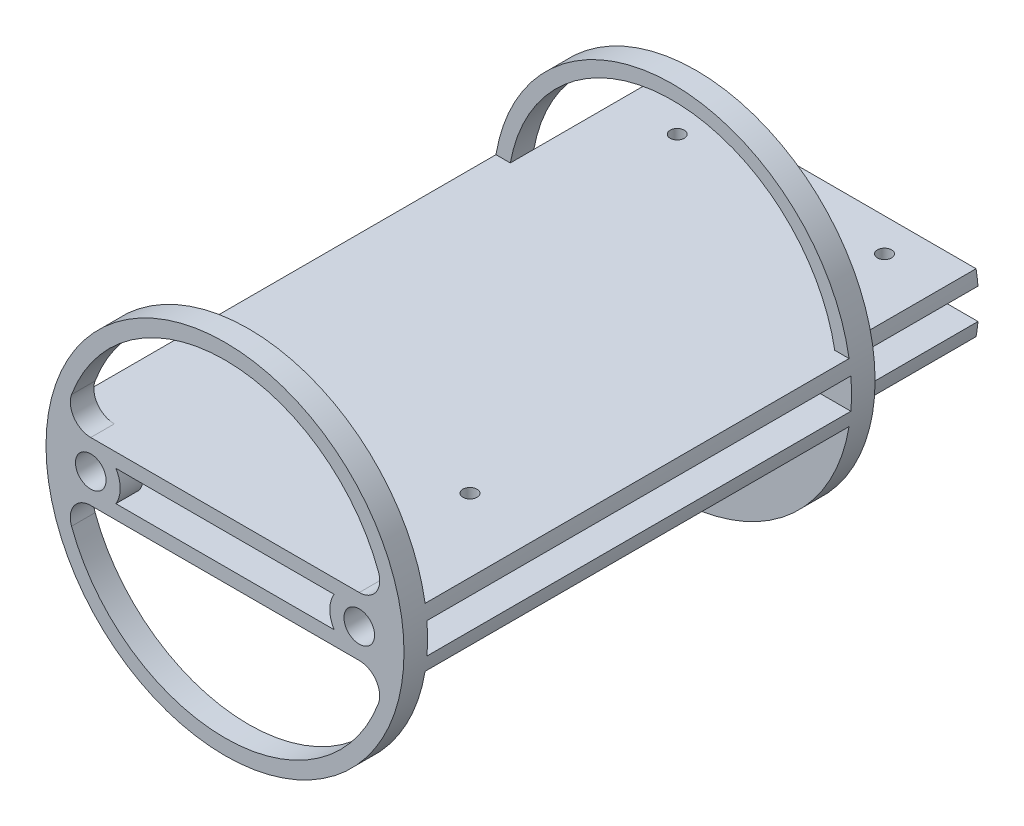
SolidWorks part; units mm, degrees
material "ABS"
ref_plane "Front Plane" through (0, 0, 0) normal (0, 0, 1) x (1, 0, 0)
ref_plane "Top Plane" through (0, 0, 0) normal (0, 1, 0) x (1, 0, 0)
ref_plane "Right Plane" through (0, 0, 0) normal (1, 0, 0) x (0, 0, -1)
sketch "Sketch1" plane through (0, 0, 0) normal (0, 0, 1) x (1, 0, 0)
  line L0 (-28.5, 0) -> (28.5, 0) construction
  line L1 (-34.5977, -3.25) -> (-33.8385, -3.25) construction
  line L2 (-28.5, -6.25) -> (28.5, -6.25)
  line L3 (-34.5977, -3.25) -> (-37.8608, -3.25) construction
  line L4 (34.5977, -3.25) -> (37.8608, -3.25) construction
  line L5 (-28.5, 6.25) -> (28.5, 6.25)
  line L6 (23.1615, 3.25) -> (-23.1615, 3.25)
  line L7 (-33.8385, -3.25) -> (-28.5, -3.25) construction
  line L8 (-23.1615, -3.25) -> (23.1615, -3.25)
  line L9 (-28.5, -3.25) -> (-23.1615, -3.25) construction
  line L10 (-34.1833, -6.25) -> (-28.5, -6.25) construction
  line L11 (23.1615, -3.25) -> (28.5, -3.25) construction
  line L12 (33.8385, -3.25) -> (34.5977, -3.25)
  line L13 (28.5, -3.25) -> (33.8385, -3.25) construction
  line L14 (28.5, -6.25) -> (34.1833, -6.25) construction
  circle A0 centre (0, 0) radius 38
  arc A1 (32.5722, 12.1083) -> (-32.5722, 12.1083) centre (0, 0) ccw
  circle A2 centre (-28.5, 0) radius 3.25
  circle A3 centre (28.5, 0) radius 3.25
  arc A4 (-23.1615, -3.25) -> (-23.1615, 3.25) centre (-28.5, 0) ccw
  arc A6 (-32.5722, 12.1083) -> (-28.5, 6.25) centre (-28.5, 10.5945) ccw
  arc A7 (-28.5, -6.25) -> (-32.5722, -12.1083) centre (-28.5, -10.5945) ccw
  arc A8 (28.5, 6.25) -> (32.5722, 12.1083) centre (28.5, 10.5945) ccw
  arc A9 (32.5722, -12.1083) -> (28.5, -6.25) centre (28.5, -10.5945) ccw
  arc A10 (34.75, 0) -> (32.5722, 12.1083) centre (0, 0) ccw construction
  arc A11 (-33.8385, -3.25) -> (-28.5, -6.25) centre (-28.5, 0) ccw construction
  arc A12 (28.5, -6.25) -> (33.8385, -3.25) centre (28.5, 0) ccw construction
  arc A13 (34.5977, -3.25) -> (34.75, 0) centre (0, 0) ccw construction
  arc A14 (-32.5722, 12.1083) -> (-34.75, 0) centre (0, 0) ccw construction
  arc A15 (-32.5722, -12.1083) -> (32.5722, -12.1083) centre (0, 0) ccw
  arc A16 (-34.5977, -3.25) -> (-34.1833, -6.25) centre (0, 0) ccw construction
  arc A17 (-34.75, 0) -> (-33.8385, -3.25) centre (-28.5, 0) ccw construction
  arc A18 (-34.75, 0) -> (-34.5977, -3.25) centre (0, 0) ccw construction
  arc A19 (-34.5977, -3.25) -> (-34.1833, -6.25) centre (0, 0) ccw construction
  arc A20 (-32.5722, -12.1083) -> (32.5722, -12.1083) centre (0, 0) ccw
  arc A21 (34.1833, -6.25) -> (34.5977, -3.25) centre (0, 0) ccw construction
  arc A22 (32.5722, 12.1083) -> (-32.5722, 12.1083) centre (0, 0) ccw
  arc A24 (23.1615, 3.25) -> (23.1615, -3.25) centre (28.5, 0) ccw
  arc A25 (-34.1833, -6.25) -> (-32.5722, -12.1083) centre (0, 0) ccw construction
  arc A26 (-34.5977, -3.25) -> (-34.1833, -6.25) centre (0, 0) ccw construction
  arc A27 (-32.5722, -12.1083) -> (32.5722, -12.1083) centre (0, 0) ccw
  arc A28 (-34.75, 0) -> (-34.5977, -3.25) centre (0, 0) ccw construction
  arc A29 (-34.75, 0) -> (-34.5977, -3.25) centre (0, 0) ccw construction
  arc A30 (-34.1833, -6.25) -> (-32.5722, -12.1083) centre (0, 0) ccw construction
  arc A31 (-34.1833, -6.25) -> (-32.5722, -12.1083) centre (0, 0) ccw construction
  arc A32 (-32.5722, 12.1083) -> (-34.75, 0) centre (0, 0) ccw construction
  arc A33 (-32.5722, 12.1083) -> (-34.75, 0) centre (0, 0) ccw construction
  arc A34 (-28.5, -6.25) -> (-23.1615, -3.25) centre (-28.5, 0) ccw construction
  arc A35 (23.1615, -3.25) -> (28.5, -6.25) centre (28.5, 0) ccw construction
  arc A36 (32.5722, -12.1083) -> (34.1833, -6.25) centre (0, 0) ccw construction
  arc A37 (32.5722, -12.1083) -> (34.1833, -6.25) centre (0, 0) ccw construction
  arc A38 (32.5722, 12.1083) -> (-32.5722, 12.1083) centre (0, 0) ccw
  arc A39 (32.5722, -12.1083) -> (34.1833, -6.25) centre (0, 0) ccw construction
  arc A40 (34.1833, -6.25) -> (34.5977, -3.25) centre (0, 0) ccw construction
  arc A41 (34.1833, -6.25) -> (34.5977, -3.25) centre (0, 0) ccw construction
  arc A42 (34.5977, -3.25) -> (34.75, 0) centre (0, 0) ccw construction
  arc A43 (34.5977, -3.25) -> (34.75, 0) centre (0, 0) ccw construction
  arc A44 (33.8385, -3.25) -> (34.75, 0) centre (28.5, 0) ccw construction
  arc A45 (34.75, 0) -> (32.5722, 12.1083) centre (0, 0) ccw construction
  arc A46 (34.75, 0) -> (32.5722, 12.1083) centre (0, 0) ccw construction
  point P8 (0, 0)
  dimension "D2" = 6.5
  dimension "D3" = 3
  dimension "D4" = 76
  dimension "D1" = 57
extrude "Boss-Extrude1" add sketch "Sketch1" along normal blind 5 contours A0 A15 A7 L2 A9 A8 L5 A6 A1 A3 A2 L6 A24 L8 A4 region at (-36.9252, 0, 0)
sketch "Sketch2" plane through (0, 0, 0) normal (0, 0, -1) x (-1, 0, 0)
  line L0 (-37.8608, -3.25) -> (37.8608, -3.25)
  line L1 (37.4825, -6.25) -> (-37.4825, -6.25)
  line L4 (-37.4825, 6.25) -> (37.4825, 6.25)
  line L5 (-37.8608, 3.25) -> (37.8608, 3.25)
  line L8 (23.1615, -3.25) -> (-23.1615, -3.25) construction
  line L9 (28.5, -6.25) -> (-28.5, -6.25) construction
  line L10 (28.5, 6.25) -> (-28.5, 6.25) construction
  line L11 (-23.1615, 3.25) -> (23.1615, 3.25) construction
  arc A1 (-37.8608, -3.25) -> (-37.4825, -6.25) centre (0, 0) ccw
  arc A2 (37.8608, 3.25) -> (37.4825, 6.25) centre (0, 0) ccw
  arc A3 (-37.4825, -6.25) -> (37.4825, -6.25) centre (0, 0) ccw construction
  arc A4 (37.4825, -6.25) -> (37.8608, -3.25) centre (0, 0) ccw
  arc A5 (37.4825, 6.25) -> (-37.4825, 6.25) centre (0, 0) ccw construction
  arc A6 (-37.4825, 6.25) -> (-37.8608, 3.25) centre (0, 0) ccw
  arc A7 (-37.8608, 3.25) -> (-37.8608, -3.25) centre (0, 0) ccw construction
  arc A8 (37.8608, -3.25) -> (37.8608, 3.25) centre (0, 0) ccw construction
  circle A9 centre (0, 0) radius 38 construction
extrude "Boss-Extrude2" add sketch "Sketch2" along normal blind 90
sketch "Sketch3" plane through (0, 0, -90) normal (0, 0, -1) x (-1, 0, 0)
  arc A1 (-28.5, 3.25) -> (-28.5, -3.25) centre (-28.5, 0) ccw construction
  arc A9 (-28.5, -3.25) -> (-28.5, 3.25) centre (-28.5, 0) ccw construction
  arc A10 (28.5, 3.25) -> (28.5, -3.25) centre (28.5, 0) ccw construction
  arc A15 (28.5, -3.25) -> (28.5, 3.25) centre (28.5, 0) ccw construction
  arc A33 (37.8608, 3.25) -> (37.4825, 6.25) centre (0, 0) ccw construction
  arc A58 (37.8608, -3.25) -> (37.8608, 3.25) centre (0, 0) ccw construction
  arc A59 (37.4825, -6.25) -> (37.8608, -3.25) centre (0, 0) ccw construction
  arc A60 (-37.4825, -6.25) -> (37.4825, -6.25) centre (0, 0) ccw construction
  arc A61 (-37.8608, -3.25) -> (-37.4825, -6.25) centre (0, 0) ccw construction
  arc A62 (-37.8608, 3.25) -> (-37.8608, -3.25) centre (0, 0) ccw construction
  arc A63 (-37.4825, 6.25) -> (-37.8608, 3.25) centre (0, 0) ccw construction
  arc A64 (37.4825, 6.25) -> (-37.4825, 6.25) centre (0, 0) ccw construction
  arc A65 (-28.5, 3.25) -> (-28.5, -3.25) centre (-28.5, 0) ccw
  arc A66 (-28.5, -3.25) -> (-28.5, 3.25) centre (-28.5, 0) ccw
  arc A67 (28.5, 3.25) -> (28.5, -3.25) centre (28.5, 0) ccw
  arc A68 (28.5, -3.25) -> (28.5, 3.25) centre (28.5, 0) ccw
  arc A69 (37.8608, 3.25) -> (37.4825, 6.25) centre (0, 0) ccw
  arc A70 (37.8608, -3.25) -> (37.8608, 3.25) centre (0, 0) ccw
  arc A71 (37.4825, -6.25) -> (37.8608, -3.25) centre (0, 0) ccw
  arc A72 (-37.4825, -6.25) -> (37.4825, -6.25) centre (0, 0) ccw
  arc A73 (-37.8608, -3.25) -> (-37.4825, -6.25) centre (0, 0) ccw
  arc A74 (-37.8608, 3.25) -> (-37.8608, -3.25) centre (0, 0) ccw
  arc A75 (-37.4825, 6.25) -> (-37.8608, 3.25) centre (0, 0) ccw
  arc A76 (37.4825, 6.25) -> (-37.4825, 6.25) centre (0, 0) ccw
extrude "Boss-Extrude3" add sketch "Sketch3" along normal blind 5
sketch "Sketch4" plane through (0, -6.25, 0) normal (0, 1, 0) x (1, 0, 0)
  line L1 (-24.5, 4) -> (24.5, 4) construction
  line L2 (-24.5, 4) -> (-24.5, 62) construction
  line L3 (-24.5, 62) -> (24.5, 62) construction
  line L4 (24.5, 4) -> (24.5, 62) construction
  line L5 (-24.5, 4) -> (24.5, 62) construction
  line L6 (-24.5, 62) -> (24.5, 4) construction
  circle A0 centre (-24.5, 62) radius 1.5
  circle A1 centre (24.5, 62) radius 1.5
  circle A2 centre (24.5, 4) radius 1.5
  circle A3 centre (-24.5, 4) radius 1.5
  point P0 (0, 33)
  dimension "D1" = 3
  dimension "D2" = 58
  dimension "D3" = 49
  dimension "D4" = 4
extrude "Cut-Extrude1" cut sketch "Sketch4" along normal up to next
sketch "Sketch6" plane through (0, 0, -95) normal (0, 0, -1) x (-1, 0, 0)
  line L0 (-34.4374, 6.25) -> (34.4374, 6.25)
  line L1 (-34.8488, 3.25) -> (34.8488, 3.25)
  line L3 (23.1615, 3.25) -> (28.5, 3.25) construction
  line L4 (-28.5, 6.25) -> (-37.4825, 6.25) construction
  arc A2 (34.8488, 3.25) -> (34.4374, 6.25) centre (0, 0) ccw
  circle A3 centre (0, 0) radius 38 construction
  arc A7 (-34.4374, 6.25) -> (-34.8488, 3.25) centre (0, 0) ccw
  point P6 (45.8259, 3.25)
  point P8 (0, 3.25)
  point P11 (-42.6272, 3.25)
  dimension "D1" = 3
extrude "Boss-Extrude5" add sketch "Sketch6" along normal blind 120 from surface starting at face at (0, 16.9133, 0)
sketch "Sketch7" plane through (0, 6.25, 0) normal (0, 1, 0) x (1, 0, 0)
  line L1 (-22, 25) -> (22, 25) construction
  line L2 (-22, 25) -> (-22, 113) construction
  line L3 (-22, 113) -> (22, 113) construction
  line L4 (22, 25) -> (22, 113) construction
  line L5 (-22, 25) -> (22, 113) construction
  line L6 (-22, 113) -> (22, 25) construction
  circle A0 centre (-22, 113) radius 1.5
  circle A1 centre (22, 113) radius 1.5
  circle A2 centre (22, 25) radius 1.5
  circle A3 centre (-22, 25) radius 1.5
  point P0 (0, 69)
  dimension "D1" = 3
  dimension "D2" = 88
  dimension "D3" = 44
  dimension "D4" = 25
extrude "Cut-Extrude2" cut sketch "Sketch7" against normal up to next
sketch "Sketch8" plane through (0, 0, -95) normal (0, 0, -1) x (-1, 0, 0)
  line L3 (-34.4374, 6.25) -> (34.4374, 6.25)
  line L5 (34.4374, 6.25) -> (-34.4374, 6.25) construction
  arc A3 (34.4374, 6.25) -> (-34.4374, 6.25) centre (0, 0) ccw
  circle A4 centre (0, 0) radius 38 construction
  dimension "D1" = 3
extrude "Cut-Extrude3" cut sketch "Sketch8" against normal up to next
sketch "Sketch9" plane through (0, 0, -95) normal (0, 0, -1) x (-1, 0, 0)
  line L0 (-34.8488, -3.25) -> (34.8488, -3.25)
  line L1 (34.4374, -6.25) -> (-34.4374, -6.25)
  arc A0 (-34.8488, -3.25) -> (-34.4374, -6.25) centre (0, 0) ccw
  arc A1 (34.4374, -6.25) -> (34.8488, -3.25) centre (0, 0) ccw
  circle A2 centre (28.5, 0) radius 3.25 construction
  dimension "D1" = 3
extrude "Boss-Extrude6" add sketch "Sketch9" along normal up to surface (25 mm away) up to face at (0, 4.7522, -120)
